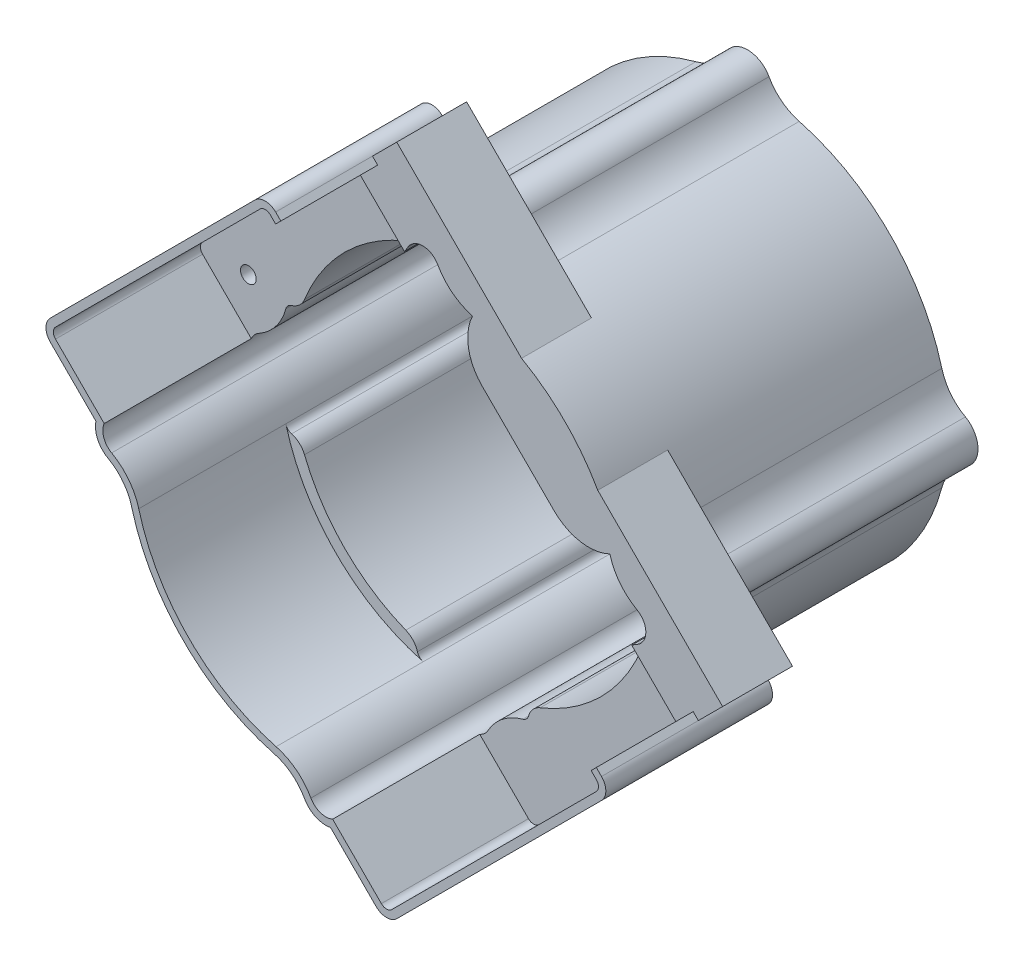
SolidWorks part; units mm, degrees
ref_plane "Ön Düzlem" through (0, 0, 0) normal (0, 0, 1) x (1, 0, 0)
ref_plane "Üst Düzlem" through (0, 0, 0) normal (0, 1, 0) x (1, 0, 0)
ref_plane "Sağ Düzlem" through (0, 0, 0) normal (1, 0, 0) x (0, 0, -1)
sketch "Çizim1" plane through (0, 0, 0) normal (0, 0, 1) x (1, 0, 0)
  circle A4 centre (0, 0) radius 33
  arc A6 (-10.5408, 39.6218) -> (-39.6218, 10.5408) centre (0, 0) ccw
  circle A7 centre (0, 42) radius 1.5
  arc A8 (4.3706, 44.4286) -> (-4.3706, 44.4286) centre (0, 42) ccw
  arc A9 (-4.3706, 44.4286) -> (-10.5408, 39.6218) centre (-13.1118, 49.2857) cw
  arc A10 (4.3706, 44.4286) -> (10.5408, 39.6218) centre (13.1118, 49.2857) ccw
  arc A11 (44.4286, 4.3706) -> (39.6218, 10.5408) centre (49.2857, 13.1118) cw
  arc A12 (44.4286, -4.3706) -> (44.4286, 4.3706) centre (42, 0) ccw
  circle A13 centre (42, 0) radius 1.5
  arc A14 (44.4286, -4.3706) -> (39.6218, -10.5408) centre (49.2857, -13.1118) ccw
  arc A15 (4.3706, -44.4286) -> (10.5408, -39.6218) centre (13.1118, -49.2857) cw
  arc A16 (-4.3706, -44.4286) -> (4.3706, -44.4286) centre (0, -42) ccw
  circle A17 centre (0, -42) radius 1.5
  arc A18 (-4.3706, -44.4286) -> (-10.5408, -39.6218) centre (-13.1118, -49.2857) ccw
  arc A19 (-44.4286, -4.3706) -> (-39.6218, -10.5408) centre (-49.2857, -13.1118) cw
  arc A20 (-44.4286, 4.3706) -> (-44.4286, -4.3706) centre (-42, 0) ccw
  circle A21 centre (-42, 0) radius 1.5
  arc A22 (-44.4286, 4.3706) -> (-39.6218, 10.5408) centre (-49.2857, 13.1118) ccw
  arc A23 (-39.6218, -10.5408) -> (-10.5408, -39.6218) centre (0, 0) ccw
  arc A24 (10.5408, -39.6218) -> (39.6218, -10.5408) centre (0, 0) ccw
  arc A25 (39.6218, 10.5408) -> (10.5408, 39.6218) centre (0, 0) ccw
  point P0 (0, 0)
  point P17 (0, 0)
  point P48 (0, 0)
  dimension "D3" = 66
  dimension "D1" = 82
  dimension "D2" = 42
  dimension "D7" = 10
  dimension "D8" = 3
  dimension "D9" = 10
  dimension "D10" = 10
  dimension "D11" = 4
extrude "Yükseklik-Ekstrüzyon1" add sketch "Çizim1" along normal blind 4
sketch "Çizim2" plane through (0, 0, 4) normal (0, 0, 1) x (1, 0, 0)
  line L0 (2.2, 0) -> (-2.2, 0) construction
  arc A0 (-44.4286, 4.3706) -> (-39.6218, 10.5408) centre (-49.2857, 13.1118) ccw construction
  arc A1 (-44.4286, 4.3706) -> (-44.4286, -4.3706) centre (-42, 0) ccw construction
  arc A2 (-39.6218, -10.5408) -> (-44.4286, -4.3706) centre (-49.2857, -13.1118) ccw construction
  arc A3 (-39.6218, -10.5408) -> (-10.5408, -39.6218) centre (0, 0) ccw construction
  arc A4 (-4.3706, -44.4286) -> (-10.5408, -39.6218) centre (-13.1118, -49.2857) ccw construction
  arc A5 (-4.3706, -44.4286) -> (4.3706, -44.4286) centre (0, -42) ccw construction
  arc A6 (10.5408, -39.6218) -> (4.3706, -44.4286) centre (13.1118, -49.2857) ccw construction
  arc A7 (10.5408, -39.6218) -> (39.6218, -10.5408) centre (0, 0) ccw construction
  arc A8 (44.4286, -4.3706) -> (39.6218, -10.5408) centre (49.2857, -13.1118) ccw construction
  arc A9 (44.4286, -4.3706) -> (44.4286, 4.3706) centre (42, 0) ccw construction
  arc A10 (39.6218, 10.5408) -> (44.4286, 4.3706) centre (49.2857, 13.1118) ccw construction
  arc A11 (39.6218, 10.5408) -> (10.5408, 39.6218) centre (0, 0) ccw construction
  arc A12 (4.3706, 44.4286) -> (10.5408, 39.6218) centre (13.1118, 49.2857) ccw construction
  arc A13 (4.3706, 44.4286) -> (-4.3706, 44.4286) centre (0, 42) ccw construction
  arc A14 (-10.5408, 39.6218) -> (-4.3706, 44.4286) centre (-13.1118, 49.2857) ccw construction
  arc A15 (-10.5408, 39.6218) -> (-39.6218, 10.5408) centre (0, 0) ccw construction
  arc A16 (-44.4286, 4.3706) -> (-39.6218, 10.5408) centre (-49.2857, 13.1118) ccw
  arc A17 (-44.4286, 4.3706) -> (-44.4286, -4.3706) centre (-42, 0) ccw
  arc A18 (-39.6218, -10.5408) -> (-44.4286, -4.3706) centre (-49.2857, -13.1118) ccw
  arc A19 (-39.6218, -10.5408) -> (-10.5408, -39.6218) centre (0, 0) ccw
  arc A20 (-4.3706, -44.4286) -> (-10.5408, -39.6218) centre (-13.1118, -49.2857) ccw
  arc A21 (-4.3706, -44.4286) -> (4.3706, -44.4286) centre (0, -42) ccw
  arc A22 (10.5408, -39.6218) -> (4.3706, -44.4286) centre (13.1118, -49.2857) ccw
  arc A23 (10.5408, -39.6218) -> (39.6218, -10.5408) centre (0, 0) ccw
  arc A24 (44.4286, -4.3706) -> (39.6218, -10.5408) centre (49.2857, -13.1118) ccw
  arc A25 (44.4286, -4.3706) -> (44.4286, 4.3706) centre (42, 0) ccw
  arc A26 (39.6218, 10.5408) -> (44.4286, 4.3706) centre (49.2857, 13.1118) ccw
  arc A27 (39.6218, 10.5408) -> (10.5408, 39.6218) centre (0, 0) ccw
  arc A28 (4.3706, 44.4286) -> (10.5408, 39.6218) centre (13.1118, 49.2857) ccw
  arc A29 (4.3706, 44.4286) -> (-4.3706, 44.4286) centre (0, 42) ccw
  arc A30 (-10.5408, 39.6218) -> (-4.3706, 44.4286) centre (-13.1118, 49.2857) ccw
  arc A31 (-10.5408, 39.6218) -> (-39.6218, 10.5408) centre (0, 0) ccw
  arc A32 (-13.7078, 34.3671) -> (-34.3671, 13.7078) centre (0, 0) ccw
  arc A33 (34.3671, 13.7078) -> (13.7078, 34.3671) centre (0, 0) ccw
  arc A34 (-34.3671, -13.7078) -> (-13.7078, -34.3671) centre (0, 0) ccw
  arc A35 (13.7078, -34.3671) -> (34.3671, -13.7078) centre (0, 0) ccw
  arc A36 (-38.1723, 10.1552) -> (-37.0048, 11.3376) centre (-36.5535, 9.7246) cw
  arc A37 (-37.0048, 11.3376) -> (-34.3671, 13.7078) centre (-38.0824, 15.1898) ccw
  arc A38 (-9.5125, 35.7563) -> (-35.7563, 9.5125) centre (0, 0) ccw construction
  arc A39 (-35.7563, -9.5125) -> (-9.5125, -35.7563) centre (0, 0) ccw construction
  arc A40 (11.3376, 37.0048) -> (13.7078, 34.3671) centre (15.1898, 38.0824) ccw
  arc A41 (10.1552, 38.1723) -> (11.3376, 37.0048) centre (9.7246, 36.5535) cw
  arc A42 (3.0594, 43.7) -> (10.1552, 38.1723) centre (13.1118, 49.2857) ccw
  arc A43 (3.0594, 43.7) -> (-3.0594, 43.7) centre (0, 42) ccw
  arc A44 (-10.1552, 38.1723) -> (-3.0594, 43.7) centre (-13.1118, 49.2857) ccw
  arc A45 (-10.1552, 38.1723) -> (-11.3376, 37.0048) centre (-9.7246, 36.5535) ccw
  arc A46 (-11.3376, 37.0048) -> (-13.7078, 34.3671) centre (-15.1898, 38.0824) cw
  arc A47 (37.0048, -11.3376) -> (34.3671, -13.7078) centre (38.0824, -15.1898) ccw
  arc A48 (-43.7, 3.0594) -> (-43.7, -3.0594) centre (-42, 0) ccw
  arc A49 (-43.7, 3.0594) -> (-38.1723, 10.1552) centre (-49.2857, 13.1118) ccw
  arc A50 (-38.1723, -10.1552) -> (-43.7, -3.0594) centre (-49.2857, -13.1118) ccw
  arc A51 (-38.1723, -10.1552) -> (-37.0048, -11.3376) centre (-36.5535, -9.7246) ccw
  arc A52 (-37.0048, -11.3376) -> (-34.3671, -13.7078) centre (-38.0824, -15.1898) cw
  arc A53 (38.1723, -10.1552) -> (37.0048, -11.3376) centre (36.5535, -9.7246) cw
  arc A54 (43.7, -3.0594) -> (38.1723, -10.1552) centre (49.2857, -13.1118) ccw
  arc A55 (43.7, -3.0594) -> (43.7, 3.0594) centre (42, 0) ccw
  arc A56 (38.1723, 10.1552) -> (43.7, 3.0594) centre (49.2857, 13.1118) ccw
  arc A57 (38.1723, 10.1552) -> (37.0048, 11.3376) centre (36.5535, 9.7246) ccw
  arc A58 (37.0048, 11.3376) -> (34.3671, 13.7078) centre (38.0824, 15.1898) cw
  arc A59 (-11.3376, -37.0048) -> (-13.7078, -34.3671) centre (-15.1898, -38.0824) ccw
  arc A60 (-10.1552, -38.1723) -> (-11.3376, -37.0048) centre (-9.7246, -36.5535) cw
  arc A61 (-3.0594, -43.7) -> (-10.1552, -38.1723) centre (-13.1118, -49.2857) ccw
  arc A62 (-3.0594, -43.7) -> (3.0594, -43.7) centre (0, -42) ccw
  arc A63 (10.1552, -38.1723) -> (3.0594, -43.7) centre (13.1118, -49.2857) ccw
  arc A64 (10.1552, -38.1723) -> (11.3376, -37.0048) centre (9.7246, -36.5535) ccw
  arc A65 (11.3376, -37.0048) -> (13.7078, -34.3671) centre (15.1898, -38.0824) cw
  arc A66 (35.7563, 9.5125) -> (9.5125, 35.7563) centre (0, 0) ccw construction
  arc A67 (9.5125, -35.7563) -> (35.7563, -9.5125) centre (0, 0) ccw construction
  point P109 (0, 0)
  dimension "D5" = 13.7078
  dimension "D1" = 4
  dimension "D2" = 4
  dimension "D3" = 1.5
  dimension "D4" = 1.5
extrude "Yükseklik-Ekstrüzyon2" add sketch "Çizim2" along normal blind 52
sketch "Çizim3" plane through (0, 0, 56) normal (0, 0, 1) x (1, 0, 0)
  line L0 (-49, -31.5) -> (-49, 31.5)
  line L1 (-45, -27.5) -> (45, -27.5) construction
  line L2 (-45, -27.5) -> (-45, 27.5) construction
  line L3 (-45, 27.5) -> (45, 27.5) construction
  line L4 (45, -27.5) -> (45, 27.5) construction
  line L5 (-45, -27.5) -> (45, 27.5) construction
  line L6 (-45, 27.5) -> (45, -27.5) construction
  line L7 (-49, 31.5) -> (-19.41, 31.5)
  line L8 (49, -31.5) -> (49, 31.5)
  line L9 (-49, -31.5) -> (-19.41, -31.5)
  line L10 (19.41, -31.5) -> (49, -31.5)
  line L11 (-49, -31.5) -> (49, -31.5) construction
  line L12 (19.41, 31.5) -> (49, 31.5)
  line L13 (-49, 31.5) -> (49, 31.5) construction
  circle A0 centre (41.15, 23.65) radius 1.6
  circle A1 centre (-41.15, -23.65) radius 1.6
  arc A2 (-38.1723, -10.1552) -> (-37.0048, -11.3376) centre (-36.5535, -9.7246) ccw construction
  arc A4 (-37.0048, 11.3376) -> (-34.3671, 13.7078) centre (-38.0824, 15.1898) ccw construction
  arc A6 (-37.0048, 11.3376) -> (-38.1723, 10.1552) centre (-36.5535, 9.7246) ccw construction
  arc A8 (-38.1723, -10.1552) -> (-43.7, -3.0594) centre (-49.2857, -13.1118) ccw construction
  arc A11 (13.7078, -34.3671) -> (34.3671, -13.7078) centre (0, 0) ccw construction
  arc A16 (38.1723, 10.1552) -> (43.7, 3.0594) centre (49.2857, 13.1118) ccw construction
  arc A17 (38.1723, 10.1552) -> (37.0048, 11.3376) centre (36.5535, 9.7246) ccw construction
  arc A18 (34.3671, 13.7078) -> (37.0048, 11.3376) centre (38.0824, 15.1898) ccw construction
  arc A27 (-13.7078, 34.3671) -> (-34.3671, 13.7078) centre (0, 0) ccw construction
  arc A28 (-43.7, 3.0594) -> (-38.1723, 10.1552) centre (-49.2857, 13.1118) ccw construction
  arc A29 (-43.7, 3.0594) -> (-43.7, -3.0594) centre (-42, 0) ccw construction
  arc A30 (-34.3671, -13.7078) -> (-37.0048, -11.3376) centre (-38.0824, -15.1898) ccw construction
  arc A31 (-34.3671, -13.7078) -> (-13.7078, -34.3671) centre (0, 0) ccw construction
  arc A32 (37.0048, -11.3376) -> (34.3671, -13.7078) centre (38.0824, -15.1898) ccw construction
  arc A33 (37.0048, -11.3376) -> (38.1723, -10.1552) centre (36.5535, -9.7246) ccw construction
  arc A34 (43.7, -3.0594) -> (38.1723, -10.1552) centre (49.2857, -13.1118) ccw construction
  arc A35 (43.7, -3.0594) -> (43.7, 3.0594) centre (42, 0) ccw construction
  arc A36 (34.3671, 13.7078) -> (13.7078, 34.3671) centre (0, 0) ccw construction
  arc A37 (19.41, -31.5) -> (34.3671, -13.7078) centre (0, 0) ccw
  arc A38 (37.0048, -11.3376) -> (34.3671, -13.7078) centre (38.0824, -15.1898) ccw
  arc A39 (37.0048, -11.3376) -> (38.1723, -10.1552) centre (36.5535, -9.7246) ccw
  arc A40 (43.7, -3.0594) -> (38.1723, -10.1552) centre (49.2857, -13.1118) ccw
  arc A41 (43.7, -3.0594) -> (43.7, 3.0594) centre (42, 0) ccw
  arc A42 (38.1723, 10.1552) -> (43.7, 3.0594) centre (49.2857, 13.1118) ccw
  arc A43 (38.1723, 10.1552) -> (37.0048, 11.3376) centre (36.5535, 9.7246) ccw
  arc A44 (34.3671, 13.7078) -> (37.0048, 11.3376) centre (38.0824, 15.1898) ccw
  arc A45 (34.3671, 13.7078) -> (19.41, 31.5) centre (0, 0) ccw
  arc A46 (-34.3671, -13.7078) -> (-19.41, -31.5) centre (0, 0) ccw
  arc A47 (-34.3671, -13.7078) -> (-37.0048, -11.3376) centre (-38.0824, -15.1898) ccw
  arc A48 (-38.1723, -10.1552) -> (-37.0048, -11.3376) centre (-36.5535, -9.7246) ccw
  arc A49 (-38.1723, -10.1552) -> (-43.7, -3.0594) centre (-49.2857, -13.1118) ccw
  arc A50 (-43.7, 3.0594) -> (-43.7, -3.0594) centre (-42, 0) ccw
  arc A51 (-43.7, 3.0594) -> (-38.1723, 10.1552) centre (-49.2857, 13.1118) ccw
  arc A52 (-37.0048, 11.3376) -> (-38.1723, 10.1552) centre (-36.5535, 9.7246) ccw
  arc A53 (-37.0048, 11.3376) -> (-34.3671, 13.7078) centre (-38.0824, 15.1898) ccw
  arc A54 (-19.41, 31.5) -> (-34.3671, 13.7078) centre (0, 0) ccw
  point P0 (0, 0)
  dimension "D4" = 3.2
  dimension "D5" = 3.85
  dimension "D6" = 3.85
  dimension "D7" = 3.85
  dimension "D8" = 3.85
  dimension "D9" = 3.2
  dimension "D1" = 90
  dimension "D2" = 55
  dimension "D3" = 4
extrude "Yükseklik-Ekstrüzyon3" [suppressed] add sketch "Çizim3" against normal blind 4
fillet "Radyus1" [suppressed] radius 14
sketch "Çizim4" plane through (0, 0, 56) normal (0, 0, 1) x (1, 0, 0)
  line L0 (-7.2702, 0) -> (5.573, 0) construction
  line L1 (12.3744, -51.2652) -> (-51.2652, 12.3744) construction
  line L2 (12.3744, -51.2652) -> (51.2652, -12.3744) construction
  line L3 (51.2652, -12.3744) -> (-12.3744, 51.2652) construction
  line L4 (-51.2652, 12.3744) -> (-12.3744, 51.2652) construction
  line L5 (12.3744, -51.2652) -> (-12.3744, 51.2652) construction
  line L6 (51.2652, -12.3744) -> (-51.2652, 12.3744) construction
  line L7 (12.3744, -58.3363) -> (58.3363, -12.3744)
  line L8 (58.3363, -12.3744) -> (45.4645, 0.4975)
  line L9 (-58.3363, 12.3744) -> (-12.3744, 58.3363)
  line L10 (12.3744, -58.3363) -> (-0.4975, -45.4645)
  line L11 (0.4975, 45.4645) -> (-12.3744, 58.3363)
  line L12 (58.3363, -12.3744) -> (-12.3744, 58.3363) construction
  line L13 (-45.4645, -0.4975) -> (-58.3363, 12.3744)
  line L14 (12.3744, -58.3363) -> (-58.3363, 12.3744) construction
  circle A0 centre (-45.8205, 12.3744) radius 1.6
  circle A1 centre (45.8205, -12.3744) radius 1.6
  arc A2 (43.7, -3.0594) -> (43.7, 3.0594) centre (42, 0) ccw construction
  arc A3 (43.7, -3.0594) -> (38.1723, -10.1552) centre (49.2857, -13.1118) ccw construction
  arc A4 (37.0048, -11.3376) -> (38.1723, -10.1552) centre (36.5535, -9.7246) ccw construction
  arc A5 (37.0048, -11.3376) -> (34.3671, -13.7078) centre (38.0824, -15.1898) ccw construction
  arc A6 (13.7078, -34.3671) -> (34.3671, -13.7078) centre (0, 0) ccw construction
  arc A7 (13.7078, -34.3671) -> (11.3376, -37.0048) centre (15.1898, -38.0824) ccw construction
  arc A8 (10.1552, -38.1723) -> (11.3376, -37.0048) centre (9.7246, -36.5535) ccw construction
  arc A9 (-3.0594, -43.7) -> (3.0594, -43.7) centre (0, -42) ccw construction
  arc A10 (10.1552, -38.1723) -> (3.0594, -43.7) centre (13.1118, -49.2857) ccw construction
  arc A11 (-43.7, 3.0594) -> (-43.7, -3.0594) centre (-42, 0) ccw construction
  arc A12 (-43.7, 3.0594) -> (-38.1723, 10.1552) centre (-49.2857, 13.1118) ccw construction
  arc A13 (-37.0048, 11.3376) -> (-38.1723, 10.1552) centre (-36.5535, 9.7246) ccw construction
  arc A14 (-37.0048, 11.3376) -> (-34.3671, 13.7078) centre (-38.0824, 15.1898) ccw construction
  arc A15 (3.0594, 43.7) -> (-3.0594, 43.7) centre (0, 42) ccw construction
  arc A16 (-10.1552, 38.1723) -> (-3.0594, 43.7) centre (-13.1118, 49.2857) ccw construction
  arc A17 (-10.1552, 38.1723) -> (-11.3376, 37.0048) centre (-9.7246, 36.5535) ccw construction
  arc A18 (-13.7078, 34.3671) -> (-11.3376, 37.0048) centre (-15.1898, 38.0824) ccw construction
  arc A19 (-13.7078, 34.3671) -> (-34.3671, 13.7078) centre (0, 0) ccw construction
  arc A20 (43.7, -3.0594) -> (45.4645, 0.4975) centre (42, 0) ccw
  arc A21 (43.7, -3.0594) -> (38.1723, -10.1552) centre (49.2857, -13.1118) ccw
  arc A22 (37.0048, -11.3376) -> (38.1723, -10.1552) centre (36.5535, -9.7246) ccw
  arc A23 (37.0048, -11.3376) -> (34.3671, -13.7078) centre (38.0824, -15.1898) ccw
  arc A24 (13.7078, -34.3671) -> (34.3671, -13.7078) centre (0, 0) ccw
  arc A25 (13.7078, -34.3671) -> (11.3376, -37.0048) centre (15.1898, -38.0824) ccw
  arc A26 (10.1552, -38.1723) -> (11.3376, -37.0048) centre (9.7246, -36.5535) ccw
  arc A27 (-0.4975, -45.4645) -> (3.0594, -43.7) centre (0, -42) ccw
  arc A28 (10.1552, -38.1723) -> (3.0594, -43.7) centre (13.1118, -49.2857) ccw
  arc A29 (-43.7, 3.0594) -> (-45.4645, -0.4975) centre (-42, 0) ccw
  arc A30 (-43.7, 3.0594) -> (-38.1723, 10.1552) centre (-49.2857, 13.1118) ccw
  arc A31 (-37.0048, 11.3376) -> (-38.1723, 10.1552) centre (-36.5535, 9.7246) ccw
  arc A32 (-37.0048, 11.3376) -> (-34.3671, 13.7078) centre (-38.0824, 15.1898) ccw
  arc A33 (0.4975, 45.4645) -> (-3.0594, 43.7) centre (0, 42) ccw
  arc A34 (-10.1552, 38.1723) -> (-3.0594, 43.7) centre (-13.1118, 49.2857) ccw
  arc A35 (-10.1552, 38.1723) -> (-11.3376, 37.0048) centre (-9.7246, 36.5535) ccw
  arc A36 (-13.7078, 34.3671) -> (-11.3376, 37.0048) centre (-15.1898, 38.0824) ccw
  arc A37 (-13.7078, 34.3671) -> (-34.3671, 13.7078) centre (0, 0) ccw
  point P0 (0, 0)
  dimension "D6" = 3.2
  dimension "D7" = 3.2
  dimension "D8" = 3.85
  dimension "D10" = 3.85
  dimension "D11" = 3.85
  dimension "D1" = 55
  dimension "D2" = 45
  dimension "D3" = 90
  dimension "D4" = 90
  dimension "D5" = 5
  dimension "D9" = 3.85
extrude "Yükseklik-Ekstrüzyon4" add sketch "Çizim4" against normal blind 4
fillet "Radyus3" radius 3 4 edges at (58.3363, -12.3744, 54) (12.3744, -58.3363, 54) (-12.3744, 58.3363, 54) (-58.3363, 12.3744, 54)
sketch "Çizim5" plane through (0, 0, 56) normal (0, 0, 1) x (1, 0, 0)
  line L0 (13.435, -55.1543) -> (55.1543, -13.435)
  line L1 (55.1543, -11.3137) -> (45.2177, -1.3771)
  line L2 (-1.3771, 45.2177) -> (-11.3137, 55.1543)
  line L3 (-13.435, 55.1543) -> (-55.1543, 13.435)
  line L4 (-55.1543, 11.3137) -> (-45.2177, 1.3771)
  line L5 (1.3771, -45.2177) -> (11.3137, -55.1543)
  line L6 (14.4957, -56.215) -> (56.215, -14.4957)
  line L7 (56.215, -10.253) -> (46.9094, -0.9475)
  line L8 (-0.9475, 46.9094) -> (-10.253, 56.215)
  line L9 (-14.4957, 56.215) -> (-56.215, 14.4957)
  line L10 (-56.215, 10.253) -> (-46.9094, 0.9475)
  line L11 (0.9475, -46.9094) -> (10.253, -56.215)
  line L12 (14.4957, -56.215) -> (56.215, -14.4957)
  line L13 (56.215, -10.253) -> (46.9094, -0.9475)
  line L14 (-0.9475, 46.9094) -> (-10.253, 56.215)
  line L15 (-14.4957, 56.215) -> (-56.215, 14.4957)
  line L16 (-56.215, 10.253) -> (-46.9094, 0.9475)
  line L17 (0.9475, -46.9094) -> (10.253, -56.215)
  arc A0 (55.1543, -13.435) -> (55.1543, -11.3137) centre (54.0937, -12.3744) ccw
  arc A1 (45.2177, -1.3771) -> (43.7, 3.0594) centre (42, 0) ccw
  arc A2 (38.1723, 10.1552) -> (43.7, 3.0594) centre (49.2857, 13.1118) ccw
  arc A3 (38.1723, 10.1552) -> (10.1552, 38.1723) centre (0, 0) ccw
  arc A4 (3.0594, 43.7) -> (10.1552, 38.1723) centre (13.1118, 49.2857) ccw
  arc A5 (3.0594, 43.7) -> (-1.3771, 45.2177) centre (0, 42) ccw
  arc A6 (-11.3137, 55.1543) -> (-13.435, 55.1543) centre (-12.3744, 54.0937) ccw
  arc A7 (-55.1543, 13.435) -> (-55.1543, 11.3137) centre (-54.0937, 12.3744) ccw
  arc A8 (-45.2177, 1.3771) -> (-43.7, -3.0594) centre (-42, 0) ccw
  arc A9 (-38.1723, -10.1552) -> (-43.7, -3.0594) centre (-49.2857, -13.1118) ccw
  arc A10 (-38.1723, -10.1552) -> (-10.1552, -38.1723) centre (0, 0) ccw
  arc A11 (-3.0594, -43.7) -> (-10.1552, -38.1723) centre (-13.1118, -49.2857) ccw
  arc A12 (-3.0594, -43.7) -> (1.3771, -45.2177) centre (0, -42) ccw
  arc A13 (11.3137, -55.1543) -> (13.435, -55.1543) centre (12.3744, -54.0937) ccw
  arc A14 (56.215, -14.4957) -> (56.215, -10.253) centre (54.0937, -12.3744) ccw
  arc A15 (46.9094, -0.9475) -> (44.4286, 4.3706) centre (42, 0) ccw
  arc A16 (39.6218, 10.5408) -> (44.4286, 4.3706) centre (49.2857, 13.1118) ccw
  arc A17 (39.6218, 10.5408) -> (10.5408, 39.6218) centre (0, 0) ccw
  arc A18 (4.3706, 44.4286) -> (10.5408, 39.6218) centre (13.1118, 49.2857) ccw
  arc A19 (4.3706, 44.4286) -> (-0.9475, 46.9094) centre (0, 42) ccw
  arc A20 (-10.253, 56.215) -> (-14.4957, 56.215) centre (-12.3744, 54.0937) ccw
  arc A21 (-56.215, 14.4957) -> (-56.215, 10.253) centre (-54.0937, 12.3744) ccw
  arc A22 (-46.9094, 0.9475) -> (-44.4286, -4.3706) centre (-42, 0) ccw
  arc A23 (-39.6218, -10.5408) -> (-44.4286, -4.3706) centre (-49.2857, -13.1118) ccw
  arc A24 (-39.6218, -10.5408) -> (-10.5408, -39.6218) centre (0, 0) ccw
  arc A25 (-4.3706, -44.4286) -> (-10.5408, -39.6218) centre (-13.1118, -49.2857) ccw
  arc A26 (-4.3706, -44.4286) -> (0.9475, -46.9094) centre (0, -42) ccw
  arc A27 (10.253, -56.215) -> (14.4957, -56.215) centre (12.3744, -54.0937) ccw
  arc A28 (56.215, -14.4957) -> (56.215, -10.253) centre (54.0937, -12.3744) ccw
  arc A29 (46.9094, -0.9475) -> (44.4286, 4.3706) centre (42, 0) ccw
  arc A30 (39.6218, 10.5408) -> (44.4286, 4.3706) centre (49.2857, 13.1118) ccw
  arc A31 (39.6218, 10.5408) -> (10.5408, 39.6218) centre (0, 0) ccw
  arc A32 (4.3706, 44.4286) -> (10.5408, 39.6218) centre (13.1118, 49.2857) ccw
  arc A33 (4.3706, 44.4286) -> (-0.9475, 46.9094) centre (0, 42) ccw
  arc A34 (-10.253, 56.215) -> (-14.4957, 56.215) centre (-12.3744, 54.0937) ccw
  arc A35 (-56.215, 14.4957) -> (-56.215, 10.253) centre (-54.0937, 12.3744) ccw
  arc A36 (-46.9094, 0.9475) -> (-44.4286, -4.3706) centre (-42, 0) ccw
  arc A37 (-39.6218, -10.5408) -> (-44.4286, -4.3706) centre (-49.2857, -13.1118) ccw
  arc A38 (-39.6218, -10.5408) -> (-10.5408, -39.6218) centre (0, 0) ccw
  arc A39 (-4.3706, -44.4286) -> (-10.5408, -39.6218) centre (-13.1118, -49.2857) ccw
  arc A40 (-4.3706, -44.4286) -> (0.9475, -46.9094) centre (0, -42) ccw
  arc A41 (10.253, -56.215) -> (14.4957, -56.215) centre (12.3744, -54.0937) ccw
  dimension "D1" = 0
  dimension "D2" = 1.5
extrude "Yükseklik-Ekstrüzyon5" add sketch "Çizim5" along normal blind 30
sketch "Çizim6" plane through (0, 0, 86) normal (0, 0, 1) x (1, 0, 0)
  line L0 (-54.0937, 10.253) -> (-55.1543, 9.1924) construction
  line L1 (10.253, -54.0937) -> (9.1924, -55.1543) construction
  line L2 (0, 0) -> (16.5689, -16.5689) construction
  line L3 (-13.435, 55.1543) -> (-55.1543, 13.435) construction
  line L4 (-9.1924, 55.1543) -> (-0.9475, 46.9094)
  line L5 (-10.253, 54.0937) -> (-9.1924, 55.1543)
  line L6 (0.9475, -46.9094) -> (10.253, -56.215)
  line L7 (14.4957, -56.215) -> (56.215, -14.4957)
  line L8 (56.215, -10.253) -> (46.9094, -0.9475)
  line L9 (-0.9475, 46.9094) -> (-10.253, 56.215)
  line L10 (-14.4957, 56.215) -> (-56.215, 14.4957)
  line L11 (-56.215, 10.253) -> (-46.9094, 0.9475)
  line L12 (0.9475, -46.9094) -> (9.1924, -55.1543) construction
  line L17 (-55.1543, 9.1924) -> (-46.9094, 0.9475) construction
  line L18 (1.3771, -45.2177) -> (11.3137, -55.1543)
  line L19 (13.435, -55.1543) -> (55.1543, -13.435)
  line L20 (55.1543, -11.3137) -> (45.2177, -1.3771)
  line L21 (-1.3771, 45.2177) -> (-11.3137, 55.1543)
  line L22 (-13.435, 55.1543) -> (-55.1543, 13.435)
  line L23 (-55.1543, 11.3137) -> (-45.2177, 1.3771)
  line L24 (1.3771, -45.2177) -> (10.253, -54.0937) construction
  line L29 (-54.0937, 10.253) -> (-45.2177, 1.3771) construction
  line L30 (-10.253, 54.0937) -> (-1.3771, 45.2177)
  line L31 (45.2177, -1.3771) -> (54.0937, -10.253)
  line L32 (54.0937, -10.253) -> (55.1543, -9.1924)
  line L33 (46.9094, -0.9475) -> (55.1543, -9.1924)
  arc A0 (44.4286, 4.3706) -> (46.9094, -0.9475) centre (42, 0) cw
  arc A1 (44.4286, 4.3706) -> (39.6218, 10.5408) centre (49.2857, 13.1118) cw
  arc A2 (10.5408, 39.6218) -> (39.6218, 10.5408) centre (0, 0) cw
  arc A3 (10.5408, 39.6218) -> (4.3706, 44.4286) centre (13.1118, 49.2857) cw
  arc A4 (-0.9475, 46.9094) -> (4.3706, 44.4286) centre (0, 42) cw
  arc A5 (-1.3771, 45.2177) -> (3.0594, 43.7) centre (0, 42) cw
  arc A6 (10.1552, 38.1723) -> (3.0594, 43.7) centre (13.1118, 49.2857) cw
  arc A7 (10.1552, 38.1723) -> (38.1723, 10.1552) centre (0, 0) cw
  arc A8 (43.7, 3.0594) -> (38.1723, 10.1552) centre (49.2857, 13.1118) cw
  arc A9 (43.7, 3.0594) -> (45.2177, -1.3771) centre (42, 0) cw
  arc A14 (10.253, -56.215) -> (14.4957, -56.215) centre (12.3744, -54.0937) ccw
  arc A15 (56.215, -14.4957) -> (56.215, -10.253) centre (54.0937, -12.3744) ccw
  arc A16 (46.9094, -0.9475) -> (44.4286, 4.3706) centre (42, 0) ccw
  arc A17 (39.6218, 10.5408) -> (44.4286, 4.3706) centre (49.2857, 13.1118) ccw
  arc A18 (39.6218, 10.5408) -> (10.5408, 39.6218) centre (0, 0) ccw
  arc A19 (4.3706, 44.4286) -> (10.5408, 39.6218) centre (13.1118, 49.2857) ccw
  arc A20 (4.3706, 44.4286) -> (-0.9475, 46.9094) centre (0, 42) ccw
  arc A21 (-10.253, 56.215) -> (-14.4957, 56.215) centre (-12.3744, 54.0937) ccw
  arc A22 (-56.215, 14.4957) -> (-56.215, 10.253) centre (-54.0937, 12.3744) ccw
  arc A23 (-46.9094, 0.9475) -> (-44.4286, -4.3706) centre (-42, 0) ccw
  arc A24 (-39.6218, -10.5408) -> (-44.4286, -4.3706) centre (-49.2857, -13.1118) ccw
  arc A25 (-39.6218, -10.5408) -> (-10.5408, -39.6218) centre (0, 0) ccw
  arc A26 (-4.3706, -44.4286) -> (-10.5408, -39.6218) centre (-13.1118, -49.2857) ccw
  arc A27 (-4.3706, -44.4286) -> (0.9475, -46.9094) centre (0, -42) ccw
  arc A37 (-46.9094, 0.9475) -> (-44.4286, -4.3706) centre (-42, 0) ccw construction
  arc A38 (-39.6218, -10.5408) -> (-44.4286, -4.3706) centre (-49.2857, -13.1118) ccw construction
  arc A39 (-39.6218, -10.5408) -> (-10.5408, -39.6218) centre (0, 0) ccw construction
  arc A40 (-4.3706, -44.4286) -> (-10.5408, -39.6218) centre (-13.1118, -49.2857) ccw construction
  arc A41 (-4.3706, -44.4286) -> (0.9475, -46.9094) centre (0, -42) ccw construction
  arc A42 (11.3137, -55.1543) -> (13.435, -55.1543) centre (12.3744, -54.0937) ccw
  arc A43 (55.1543, -13.435) -> (55.1543, -11.3137) centre (54.0937, -12.3744) ccw
  arc A44 (45.2177, -1.3771) -> (43.7, 3.0594) centre (42, 0) ccw
  arc A45 (38.1723, 10.1552) -> (43.7, 3.0594) centre (49.2857, 13.1118) ccw
  arc A46 (38.1723, 10.1552) -> (10.1552, 38.1723) centre (0, 0) ccw
  arc A47 (3.0594, 43.7) -> (10.1552, 38.1723) centre (13.1118, 49.2857) ccw
  arc A48 (3.0594, 43.7) -> (-1.3771, 45.2177) centre (0, 42) ccw
  arc A49 (-11.3137, 55.1543) -> (-13.435, 55.1543) centre (-12.3744, 54.0937) ccw
  arc A50 (-55.1543, 13.435) -> (-55.1543, 11.3137) centre (-54.0937, 12.3744) ccw
  arc A51 (-45.2177, 1.3771) -> (-43.7, -3.0594) centre (-42, 0) ccw
  arc A52 (-38.1723, -10.1552) -> (-43.7, -3.0594) centre (-49.2857, -13.1118) ccw
  arc A53 (-38.1723, -10.1552) -> (-10.1552, -38.1723) centre (0, 0) ccw
  arc A54 (-3.0594, -43.7) -> (-10.1552, -38.1723) centre (-13.1118, -49.2857) ccw
  arc A55 (-3.0594, -43.7) -> (1.3771, -45.2177) centre (0, -42) ccw
  arc A65 (-45.2177, 1.3771) -> (-43.7, -3.0594) centre (-42, 0) ccw construction
  arc A66 (-38.1723, -10.1552) -> (-43.7, -3.0594) centre (-49.2857, -13.1118) ccw construction
  arc A67 (-38.1723, -10.1552) -> (-10.1552, -38.1723) centre (0, 0) ccw construction
  arc A68 (-3.0594, -43.7) -> (-10.1552, -38.1723) centre (-13.1118, -49.2857) ccw construction
  arc A69 (-3.0594, -43.7) -> (1.3771, -45.2177) centre (0, -42) ccw construction
  dimension "D3" = 91
  dimension "D4" = 3
  dimension "D1" = 0
  dimension "D2" = 0
extrude "Kes-Ekstrüzyon1" cut sketch "Çizim6" against normal blind 19.75
sketch "Çizim7" plane through (0, 0, 66.25) normal (0, 0, 1) x (1, 0, 0)
  line L0 (45.2177, -1.3771) -> (54.0937, -10.253) construction
  line L1 (-10.253, 54.0937) -> (-1.3771, 45.2177) construction
  line L2 (45.2177, -1.3771) -> (54.0937, -10.253)
  line L3 (-10.253, 54.0937) -> (-1.3771, 45.2177)
  line L4 (55.1543, -11.3137) -> (54.0937, -10.253) construction
  line L5 (-10.253, 54.0937) -> (-11.3137, 55.1543) construction
  line L6 (55.1543, -11.3137) -> (54.0937, -10.253)
  line L7 (-10.253, 54.0937) -> (-11.3137, 55.1543)
  line L8 (-13.435, 55.1543) -> (-14.8492, 53.7401)
  line L9 (55.1543, -13.435) -> (53.7401, -14.8492)
  line L10 (13.435, -55.1543) -> (55.1543, -13.435) construction
  line L11 (53.7401, -14.8492) -> (42.6267, -3.7358)
  line L12 (10.1552, 38.1723) -> (5.4369, 33.454)
  line L13 (38.1723, 10.1552) -> (33.454, 5.4369)
  line L14 (-3.7358, 42.6267) -> (-14.8492, 53.7401)
  line L15 (33.454, 5.4369) -> (5.4369, 33.454)
  arc A0 (43.7, -3.0594) -> (45.2177, -1.3771) centre (42, 0) ccw construction
  arc A1 (-1.3771, 45.2177) -> (-3.0594, 43.7) centre (0, 42) ccw construction
  arc A2 (38.1723, 10.1552) -> (10.1552, 38.1723) centre (0, 0) ccw construction
  arc A3 (43.7, -3.0594) -> (38.1723, -10.1552) centre (49.2857, -13.1118) ccw construction
  arc A4 (-10.1552, 38.1723) -> (-3.0594, 43.7) centre (-13.1118, 49.2857) ccw construction
  arc A5 (55.1543, -13.435) -> (55.1543, -11.3137) centre (54.0937, -12.3744) ccw construction
  arc A6 (-11.3137, 55.1543) -> (-13.435, 55.1543) centre (-12.3744, 54.0937) ccw construction
  arc A7 (38.1723, 10.1552) -> (10.1552, 38.1723) centre (0, 0) ccw
  arc A8 (55.1543, -13.435) -> (55.1543, -11.3137) centre (54.0937, -12.3744) ccw
  arc A9 (-11.3137, 55.1543) -> (-13.435, 55.1543) centre (-12.3744, 54.0937) ccw
  arc A10 (43.7, -3.0594) -> (42.6267, -3.7358) centre (49.2857, -13.1118) ccw
  arc A11 (-3.7358, 42.6267) -> (-3.0594, 43.7) centre (-13.1118, 49.2857) ccw
  arc A12 (-1.3771, 45.2177) -> (-3.0594, 43.7) centre (0, 42) ccw
  arc A13 (43.7, -3.0594) -> (45.2177, -1.3771) centre (42, 0) ccw
  dimension "D1" = 3.5
extrude "Yükseklik-Ekstrüzyon6" add sketch "Çizim7" against normal up to surface (10.25 mm away) up to face at (-26.7449, 26.7449, 56)
sketch "Çizim8" plane through (0, 0, 56) normal (0, 0, -1) x (-1, 0, 0)
  line L3 (-38.1723, 10.1552) -> (-33.454, 5.4369)
  line L4 (-33.454, 5.4369) -> (-5.4369, 33.454)
  line L5 (-5.4369, 33.454) -> (-10.1552, 38.1723)
  line L6 (-38.1723, 10.1552) -> (-33.454, 5.4369)
  line L7 (-33.454, 5.4369) -> (-5.4369, 33.454)
  line L8 (-5.4369, 33.454) -> (-10.1552, 38.1723)
  arc A5 (-37.0048, 11.3376) -> (-38.1723, 10.1552) centre (-36.5535, 9.7246) ccw
  arc A6 (-10.1552, 38.1723) -> (-11.3376, 37.0048) centre (-9.7246, 36.5535) ccw
  arc A7 (-13.7078, 34.3671) -> (-11.3376, 37.0048) centre (-15.1898, 38.0824) ccw
  arc A8 (-13.7078, 34.3671) -> (-34.3671, 13.7078) centre (0, 0) ccw
  arc A9 (-37.0048, 11.3376) -> (-34.3671, 13.7078) centre (-38.0824, 15.1898) ccw
  arc A10 (-37.0048, 11.3376) -> (-38.1723, 10.1552) centre (-36.5535, 9.7246) ccw
  arc A11 (-10.1552, 38.1723) -> (-11.3376, 37.0048) centre (-9.7246, 36.5535) ccw
  arc A12 (-13.7078, 34.3671) -> (-11.3376, 37.0048) centre (-15.1898, 38.0824) ccw
  arc A13 (-13.7078, 34.3671) -> (-34.3671, 13.7078) centre (0, 0) ccw
  arc A14 (-37.0048, 11.3376) -> (-34.3671, 13.7078) centre (-38.0824, 15.1898) ccw
  dimension "D1" = 0
extrude "Yükseklik-Ekstrüzyon7" add sketch "Çizim8" along normal up to surface (56 mm away) up to face at (1.5, -42, 0)
fillet "Radyus4" radius 10 2 edges at (33.454, 5.4369, 35.125) (5.4369, 33.454, 35.125)
sketch "Çizim9" plane through (0, 0, 66.25) normal (0, 0, 1) x (1, 0, 0)
  line L0 (-0.9475, 46.9094) -> (-9.1924, 55.1543) construction
  line L1 (56.215, -10.253) -> (55.1543, -9.1924) construction
  line L2 (55.1543, -9.1924) -> (46.9094, -0.9475) construction
  line L3 (-9.1924, 55.1543) -> (-10.253, 56.215) construction
  line L4 (-9.1924, 55.1543) -> (-10.253, 56.215)
  line L5 (-0.9475, 46.9094) -> (-9.1924, 55.1543)
  line L6 (56.215, -10.253) -> (55.1543, -9.1924)
  line L7 (55.1543, -9.1924) -> (46.9094, -0.9475)
  line L8 (56.215, -10.253) -> (61.1647, -5.3033)
  line L9 (-10.253, 56.215) -> (-5.3033, 61.1647)
  line L10 (61.1647, -5.3033) -> (35.7009, 20.1606)
  line L11 (20.1606, 35.7009) -> (-5.3033, 61.1647)
  arc A0 (4.3706, 44.4286) -> (-0.9475, 46.9094) centre (0, 42) ccw construction
  arc A1 (4.3706, 44.4286) -> (10.5408, 39.6218) centre (13.1118, 49.2857) ccw construction
  arc A2 (39.6218, 10.5408) -> (10.5408, 39.6218) centre (0, 0) ccw construction
  arc A3 (39.6218, 10.5408) -> (44.4286, 4.3706) centre (49.2857, 13.1118) ccw construction
  arc A4 (46.9094, -0.9475) -> (44.4286, 4.3706) centre (42, 0) ccw construction
  arc A5 (4.3706, 44.4286) -> (-0.9475, 46.9094) centre (0, 42) ccw
  arc A6 (4.3706, 44.4286) -> (10.5408, 39.6218) centre (13.1118, 49.2857) ccw
  arc A7 (39.6218, 10.5408) -> (35.7009, 20.1606) centre (0, 0) ccw
  arc A8 (39.6218, 10.5408) -> (44.4286, 4.3706) centre (49.2857, 13.1118) ccw
  arc A9 (46.9094, -0.9475) -> (44.4286, 4.3706) centre (42, 0) ccw
  arc A10 (20.1606, 35.7009) -> (10.5408, 39.6218) centre (0, 0) ccw
  dimension "D1" = 7
extrude "Yükseklik-Ekstrüzyon8" add sketch "Çizim9" against normal up to surface (14.25 mm away) up to face at (47.4205, -12.3744, 52)
